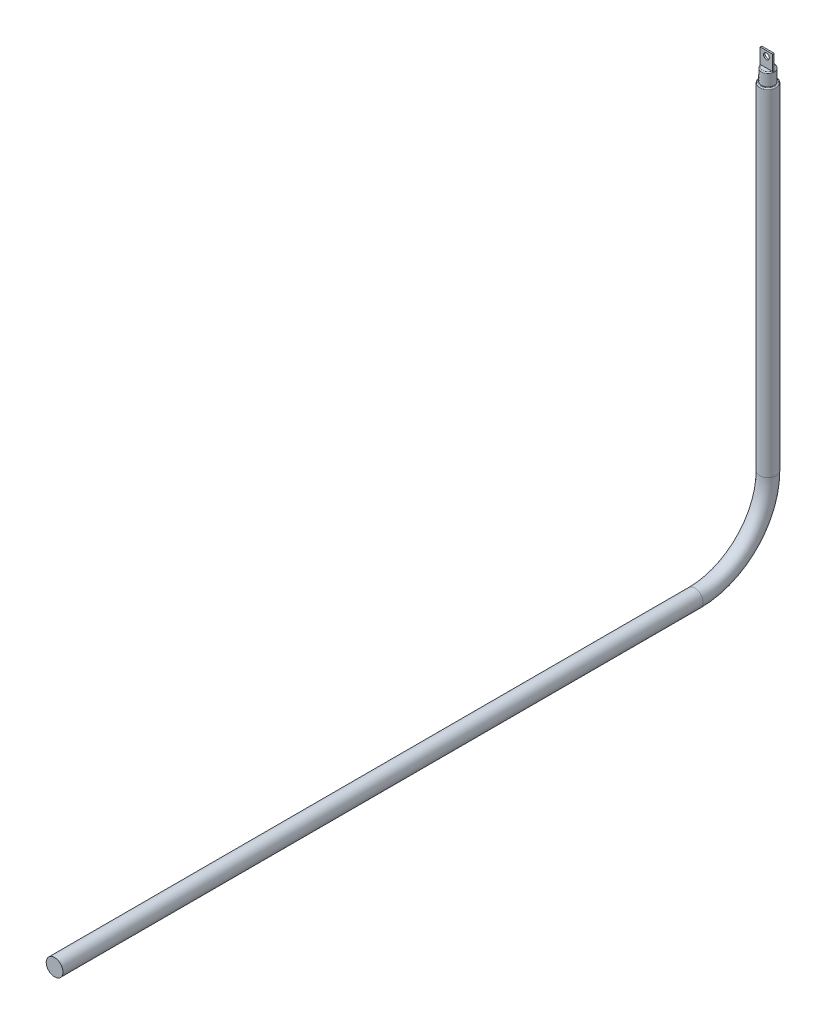
SolidWorks part; units mm, degrees
ref_plane "Alzado" through (0, 0, 0) normal (0, 0, 1) x (1, 0, 0)
ref_plane "Planta" through (0, 0, 0) normal (0, 1, 0) x (1, 0, 0)
ref_plane "Vista lateral" through (0, 0, 0) normal (1, 0, 0) x (0, 0, -1)
sketch3d "Croquis3D1"
  line L0 (1184.694, -317.2662, 2234.9932) -> (1184.694, -961.6676, 2234.9932)
  line L2 (1184.694, -1101.6676, 2374.9932) -> (1184.694, -1101.6676, 3598.953)
  line L3 (1184.694, -317.2662, 2234.9932) -> (975.004, -317.2662, 2234.9932) construction
  arc A0 (1184.694, -961.6676, 2234.9932) -> (1184.694, -1101.6676, 2374.9932) centre (1184.694, -961.6676, 2374.9932) ccw
  point P7 (1184.694, -1101.6676, 2234.9932)
  point P8 (1044.694, -961.6676, 2374.9932)
  dimension "D1" = 140
  dimension "D2" = 209.69
sweep "Barrer1" add path "Croquis3D1" circular profile diameter 32 parameters "D3"=32
sketch "Croquis21" plane through (0, -317.2662, 0) normal (0, 1, 0) x (1, 0, 0)
  line L0 (1168.694, -2234.9932) -> (1200.694, -2234.9932) construction
  circle A0 centre (1184.694, -2234.9932) radius 16 construction
ref_plane "Plano1" through (0, 0, 2234.9932) normal (0, 0, 1) x (1, 0, 0)
sketch "Croquis22" plane through (0, 0, 2234.9932) normal (0, 0, 1) x (1, 0, 0)
  line L0 (1184.694, -317.2662) -> (1184.694, -294.3213) construction
  line L1 (1168.694, -317.2662) -> (1200.694, -317.2662) construction
  line L3 (1172.694, -264.3213) -> (1196.694, -264.3213)
  line L4 (1172.694, -264.3213) -> (1172.694, -294.3213)
  line L5 (1172.694, -294.3213) -> (1196.694, -294.3213)
  line L6 (1196.694, -264.3213) -> (1196.694, -294.3213)
  circle A0 centre (1184.694, -273.8105) radius 5.5
  point P5 (1184.694, -264.5684)
  point P10 (1184.694, -270.0749)
  point P11 (1184.694, -278.1388)
  point P13 (1184.694, -273.8105)
  point P15 (1184.694, -279.3213)
  dimension "D1" = 11
  dimension "D2" = 24
  dimension "D3" = 30
extrude "Saliente-Extruir1" add sketch "Croquis22" along normal blind 3 separate body
sketch "Croquis23" plane through (0, -317.2662, 0) normal (0, 1, 0) x (1, 0, 0)
  circle A0 centre (1184.694, -2234.9932) radius 12.5
  dimension "D1" = 25
extrude "Saliente-Extruir2" add sketch "Croquis23" along normal blind 24 draft 0.1
fillet "Redondeo1" radius 2 1 edges at (1172.2359, -293.2662, 2234.9932)
fillet "Redondeo2" radius 2 1 edges at (1168.694, -317.2662, 2234.9932)
